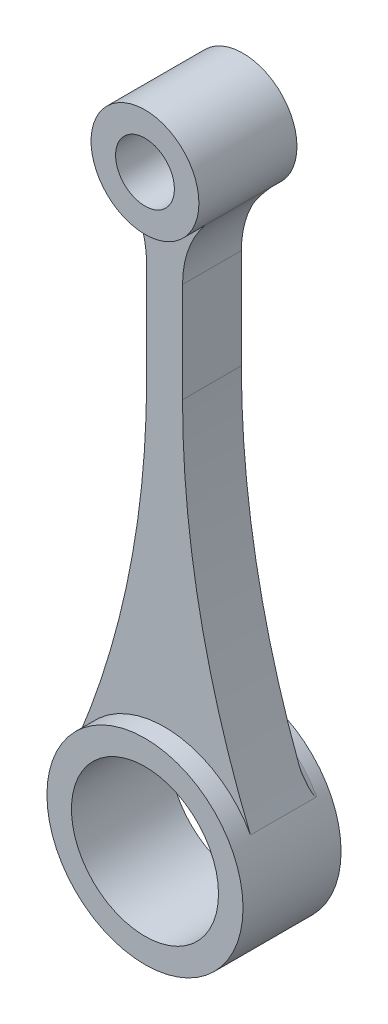
SolidWorks part; units mm, degrees
ref_plane "Płaszczyzna przednia" through (0, 0, 0) normal (0, 0, 1) x (1, 0, 0)
ref_plane "Płaszczyzna górna" through (0, 0, 0) normal (0, 1, 0) x (1, 0, 0)
ref_plane "Płaszczyzna prawa" through (0, 0, 0) normal (1, 0, 0) x (0, 0, -1)
sketch "Szkic1" plane through (0, 0, 0) normal (0, 0, 1) x (1, 0, 0)
  circle A0 centre (0, 107.6051) radius 6
  circle A1 centre (0, 107.6051) radius 11
  circle A2 centre (0, -12.3949) radius 15
  circle A3 centre (0, -12.3949) radius 20
  point P6 (0, 0)
  dimension "D1" = 12
  dimension "D2" = 22
  dimension "D3" = 30
  dimension "D4" = 40
  dimension "D5" = 120
extrude "Dodanie-wyciągnięcie1" add sketch "Szkic1" along normal mid plane 20
sketch "Szkic8" plane through (0, 0, 0) normal (0, 0, 1) x (1, 0, 0)
  line L0 (0, 107.6051) -> (0, -12.3949) construction
  line L1 (-3.6621, 97.2326) -> (-3.6621, 67.2326)
  line L2 (3.6621, 97.2326) -> (3.6621, 67.2326)
  circle A0 centre (0, -12.3949) radius 20 construction
  circle A1 centre (0, 107.6051) radius 11 construction
  arc A2 (17.5173, -2.7439) -> (-17.5173, -2.7439) centre (0, -12.3949) ccw
  arc A3 (-3.6621, 97.2326) -> (3.6621, 97.2326) centre (0, 107.6051) ccw
  arc A4 (3.6621, 67.2326) -> (17.5173, -2.7439) centre (187.2998, 67.2326) ccw
  arc A5 (-3.6621, 67.2326) -> (-17.5173, -2.7439) centre (-187.2998, 67.2326) cw
  point P18 (0, 0)
  point P19 (0, 0)
  point P20 (0, 0)
  point P21 (-17.5173, -2.7439)
  point P22 (0, 0)
  dimension "D1" = 30
  dimension "D2" = 30
extrude "Dodanie-wyciągnięcie2" add sketch "Szkic8" along normal mid plane 12 contours A2 A5 L1 A3 L2 A4
fillet "Zaokrąglenie6" radius 1.5 2 edges at (0, 96.6051, -6) (0, 7.6051, -6)
fillet "Zaokrąglenie7" radius 20 2 edges at (3.6621, 97.2326, -0.75) (-3.6621, 97.2326, -0.75)
